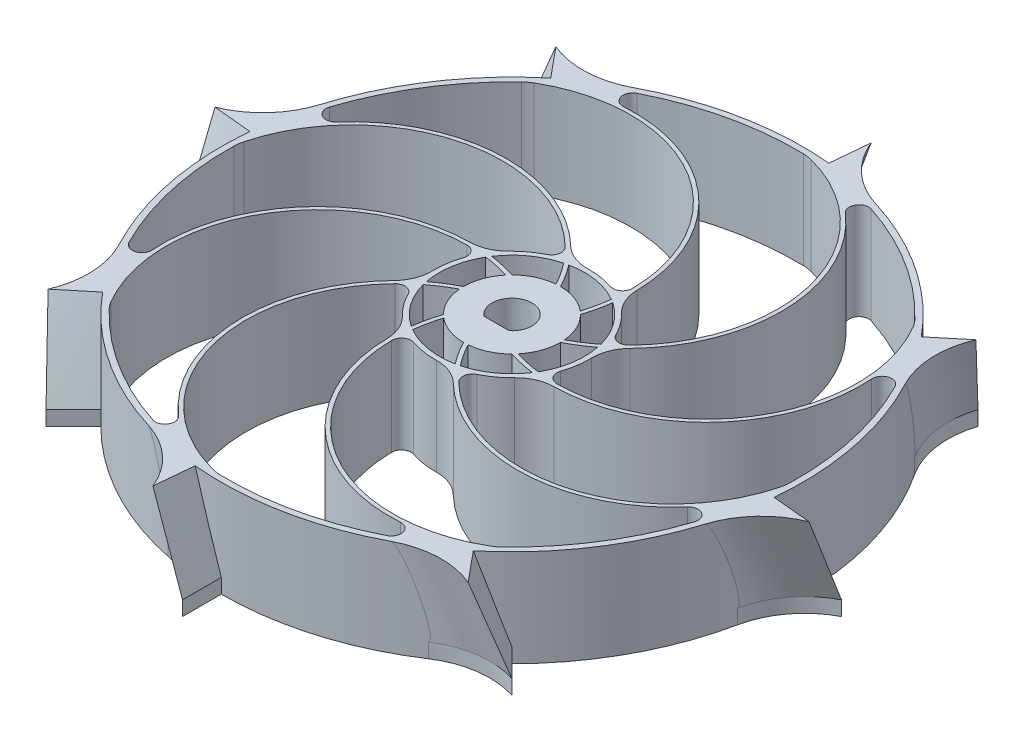
SolidWorks part; units mm, degrees
material "PET"
ref_plane "Front Plane" through (0, 0, 0) normal (0, 0, 1) x (1, 0, 0)
ref_plane "Top Plane" through (0, 0, 0) normal (0, 1, 0) x (1, 0, 0)
ref_plane "Right Plane" through (0, 0, 0) normal (1, 0, 0) x (0, 0, -1)
ref_plane "Plane1" through (0, 3, 0) normal (0, 1, 0) x (1, 0, 0)
sketch "Sketch1" plane through (0, 0, 0) normal (0, 1, 0) x (1, 0, 0)
  line L0 (-2.603, -3.2) -> (2.603, -3.2)
  arc A0 (2.603, -3.2) -> (-2.603, -3.2) centre (0, 0) ccw
  circle A1 centre (0, 0) radius 60
  circle A28 centre (0, 0) radius 10
  circle A29 centre (0, 0) radius 58.8
  point P78 (0, 0)
  dimension "D1" = 8.25
  dimension "D2" = 120
  dimension "D3" = 20
  dimension "D7" = 3.2
  dimension "D4" = 1.2
extrude "Boss-Extrude1" add sketch "Sketch1" along normal blind 20 contours A1 A29 | A28 A0 L0 region at (-59.8303, 0, 0) region at (-9.7172, 0, 0)
sketch "Sketch4" plane through (0, 0, 0) normal (0, 1, 0) x (1, 0, 0)
  line L0 (-9.6325, -0.7106) -> (-10, 0)
  line L1 (0.1172, -59.2086) -> (0, -60)
  arc A0 (0, -60) -> (-10, 0) centre (4.6819, -28.3864) cw
  circle A1 centre (0, 0) radius 60 construction
  circle A2 centre (0, 0) radius 10 construction
  arc A3 (0.1172, -59.2086) -> (-9.6325, -0.7106) centre (4.6819, -28.3864) cw
  dimension "D1" = 0.8
extrude "Boss-Extrude4" add sketch "Sketch4" along normal up to surface (20 mm away) up to face at (0, 20, 58.8)
ref_axis "Axis1" through (0, 21, 0) along (0, -1, 0)
pattern_circular "CirPattern1" count 8 over 360 about axis through (0, 21, 0) along (0, -1, 0) of "Boss-Extrude4"
sketch "Sketch2" plane through (0, 0, 0) normal (0, 1, 0) x (1, 0, 0)
  circle A0 centre (0, 0) radius 15
  circle A1 centre (0, 0) radius 16
  dimension "D1" = 30
  dimension "D2" = 1
extrude "Boss-Extrude2" add sketch "Sketch2" along normal up to surface (20 mm away) up to face at (21.0377, 20, 26.1005)
sketch "Sketch3" plane through (0, 3, 0) normal (0, 1, 0) x (1, 0, 0)
  line L0 (0, -60) -> (0, -68)
  line L6 (-42.4264, -42.4264) -> (-48.0833, -48.0833)
  line L7 (-60, 0) -> (-68, 0)
  line L8 (-42.4264, 42.4264) -> (-48.0833, 48.0833)
  line L9 (0, 60) -> (0, 68)
  line L10 (42.4264, 42.4264) -> (48.0833, 48.0833)
  line L11 (60, 0) -> (68, 0)
  line L12 (42.4264, -42.4264) -> (48.0833, -48.0833)
  arc A0 (-48.0833, -48.0833) -> (-50.1745, -32.9017) centre (-65.1067, -42.6934) ccw
  arc A1 (0, -68) -> (-12.2137, -58.7437) centre (-15.8486, -76.2261) ccw
  arc A13 (-68, 0) -> (-58.7437, 12.2137) centre (-76.2261, 15.8486) ccw
  arc A15 (-48.0833, 48.0833) -> (-32.9017, 50.1745) centre (-42.6934, 65.1067) ccw
  circle A17 centre (0, 0) radius 60 construction
  circle A18 centre (0, 0) radius 60
  arc A19 (0, 68) -> (12.2137, 58.7437) centre (15.8486, 76.2261) ccw
  arc A20 (48.0833, 48.0833) -> (50.1745, 32.9017) centre (65.1067, 42.6934) ccw
  arc A21 (68, 0) -> (58.7437, -12.2137) centre (76.2261, -15.8486) ccw
  arc A22 (48.0833, -48.0833) -> (32.9017, -50.1745) centre (42.6934, -65.1067) ccw
  arc A23 (-58.7437, 12.2137) -> (-60, 0) centre (0, 0) ccw
  arc A24 (60, 0) -> (58.7437, -12.2137) centre (0, 0) cw
  point P30 (0, 0)
  point P33 (-2.1651, 1.25)
  point P42 (0, 0)
  dimension "D1" = 8
  dimension "D2" = 8
fillet "Fillet1" radius 2 16 edges at (7.6573, 10, -14.0487) (15.3485, 10, -4.5193) (14.0487, 10, 7.6573) (4.5193, 10, 15.3485) (-7.6573, 10, 14.0487) (-15.3485, 10, 4.5193) (-14.0487, 10, -7.6573) (-4.5193, 10, -15.3485) (-6.0542, 10, 58.4875) (37.0759, 10, 45.6379) (58.4875, 10, 6.0542) (45.6379, 10, -37.0759) (6.0542, 10, -58.4875) (-37.0759, 10, -45.6379) (-58.4875, 10, -6.0542) (-45.6379, 10, 37.0759)
fillet "Fillet2" radius 8 16 edges at (-8.4195, 10, 13.6056) (-15.5741, 10, 3.6672) (-13.6056, 10, -8.4195) (-3.6672, 10, -15.5741) (8.4195, 10, -13.6056) (15.5741, 10, -3.6672) (13.6056, 10, 8.4195) (3.6672, 10, 15.5741) (-58.7555, 10, -2.2868) (-39.9294, 10, -43.1635) (2.2868, 10, -58.7555) (43.1635, 10, -39.9294) (58.7555, 10, 2.2868) (39.9294, 10, 43.1635) (-2.2868, 10, 58.7555) (-43.1635, 10, 39.9294)
sketch "Sketch5" plane through (0, 20, 0) normal (0, 1, 0) x (1, 0, 0)
  line L0 (-5.6487, -59.7335) -> (-6.4019, -67.698)
  line L6 (-46.2322, -38.2437) -> (-52.3965, -43.3429)
  line L7 (-59.7335, 5.6487) -> (-67.698, 6.4019)
  line L8 (-38.2437, 46.2322) -> (-43.3429, 52.3965)
  line L9 (5.6487, 59.7335) -> (6.4019, 67.698)
  line L10 (46.2322, 38.2437) -> (52.3965, 43.3429)
  line L11 (59.7335, -5.6487) -> (67.698, -6.4019)
  line L12 (38.2437, -46.2322) -> (43.3429, -52.3965)
  line L13 (0, 0) -> (-5.6487, -59.7335) construction
  arc A0 (-52.3965, -43.3429) -> (-53.0492, -28.0319) centre (-68.8369, -36.3743) ccw
  arc A1 (-6.4019, -67.698) -> (-17.6899, -57.333) centre (-22.9545, -74.3955) ccw
  arc A13 (-67.698, 6.4019) -> (-57.333, 17.6899) centre (-74.3955, 22.9545) ccw
  arc A15 (-43.3429, 52.3965) -> (-28.0319, 53.0492) centre (-36.3743, 68.8369) ccw
  circle A18 centre (0, 0) radius 60
  arc A19 (6.4019, 67.698) -> (17.6899, 57.333) centre (22.9545, 74.3955) ccw
  arc A20 (52.3965, 43.3429) -> (53.0492, 28.0319) centre (68.8369, 36.3743) ccw
  arc A21 (67.698, -6.4019) -> (57.333, -17.6899) centre (74.3955, -22.9545) ccw
  arc A22 (43.3429, -52.3965) -> (28.0319, -53.0492) centre (36.3743, -68.8369) ccw
  arc A23 (-57.333, 17.6899) -> (-59.7335, 5.6487) centre (0, 0) ccw
  arc A24 (59.7335, -5.6487) -> (57.333, -17.6899) centre (0, 0) cw
  circle A25 centre (0, 0) radius 60 construction
  point P30 (0, 0)
  point P33 (-2.1651, 1.25)
  point P42 (0, 0)
  dimension "D3" = 12.2782
  dimension "D1" = 8
  dimension "D2" = 8
loft "Loft1" add section "Sketch3" section "Sketch5" connector at (0, 3, 60) connector at (-5.6487, 20, 59.7335)
extrude "Boss-Extrude6" add sketch "Sketch3<82>" against normal blind 3 contours A18 A1 L0 region at (-2.8725, 3, 62.1395)
sketch "Sketch3<82>" plane through (0, 3, 0) normal (0, 1, 0) x (1, 0, 0) same geometry as "Sketch3"
pattern_circular "CirPattern2" count 8 over 360 about axis through (0, 21, 0) along (0, -1, 0) of "Boss-Extrude6", "Loft1"
